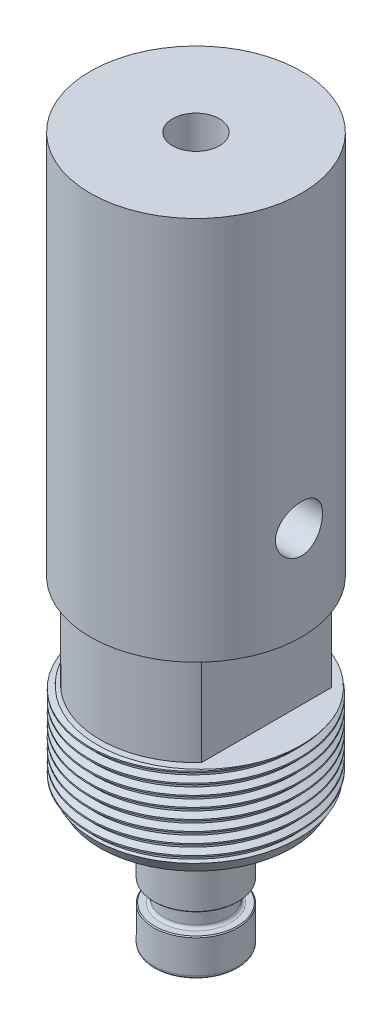
SolidWorks part; units mm, degrees
ref_plane "Front Plane" through (0, 0, 0) normal (0, 0, 1) x (1, 0, 0)
ref_plane "Top Plane" through (0, 0, 0) normal (0, 1, 0) x (1, 0, 0)
ref_plane "Right Plane" through (0, 0, 0) normal (1, 0, 0) x (0, 0, -1)
sketch "Sketch1" plane through (0, 0, 0) normal (0, 0, 1) x (1, 0, 0)
  line L0 (0, 50.6579) -> (0, -11.3733) construction
  line L1 (1.27, 0) -> (1.27, 87.1402)
  line L2 (1.27, 87.1402) -> (2.286, 88.9)
  line L3 (2.286, 88.9) -> (3.175, 88.9)
  line L4 (3.175, 88.9) -> (3.175, 95.25)
  line L5 (3.175, 95.25) -> (14.2875, 95.25)
  line L6 (14.2875, 95.25) -> (14.2875, 43.2816)
  line L7 (14.2875, 43.2816) -> (12.954, 43.2816)
  line L8 (12.954, 43.2816) -> (12.954, 30.5816)
  line L9 (12.954, 30.5816) -> (14.224, 30.5816)
  line L10 (14.224, 30.5816) -> (14.224, 20.0813)
  line L11 (14.224, 20.0813) -> (12.954, 17.8816)
  line L12 (12.954, 17.8816) -> (10.16, 17.8816)
  line L13 (10.16, 17.8816) -> (10.16, 19.3548)
  line L14 (10.16, 19.3548) -> (5.715, 19.3548)
  line L15 (5.715, 19.3548) -> (5.715, 7.8994)
  line L16 (5.715, 7.8994) -> (4.3434, 7.8994)
  line L17 (4.3434, 7.8994) -> (4.3434, 5.08)
  line L18 (5.715, 0) -> (1.27, 0)
  line L19 (4.3434, 5.08) -> (5.715, 5.08)
  line L20 (5.715, 5.08) -> (5.715, 0)
  point P20 (5.0292, 5.08)
  point P27 (13.589, 30.5816)
  dimension "D1" = 2.54
  dimension "D2" = 28.575
  dimension "D3" = 95.25
  dimension "D4" = 6.35
  dimension "D5" = 6.35
  dimension "D6" = 0.889
  dimension "D7" = 30
  dimension "D8" = 11.43
  dimension "D9" = 2.8194
  dimension "D10" = 8.6868
  dimension "D11" = 5.08
  dimension "D12" = 4.445
  dimension "D13" = 1.4732
  dimension "D14" = 11.4554
  dimension "D15" = 28.448
  dimension "D16" = 1.27
  dimension "D17" = 12.7
  dimension "D18" = 1.27
  dimension "D19" = 12.7
revolve "Revolve1" add sketch "Sketch1" angle 360 about L0
fillet "Fillet1" radius 0.508 1 edges at (0, 0, 5.715)
chamfer "Chamfer1" distance 0.127 angle 45 3 edges at (0, 17.8816, 10.16) (0, 5.08, 5.715) (0, 7.8994, 5.715)
fillet "Fillet2" radius 0.4064 4 edges at (0, 19.3548, 10.16) (0, 19.3548, 5.715) (0, 7.8994, 4.3434) (0, 5.08, 4.3434)
thread "Thread1" pitch 1.4111 method cut profile "Thread Profile1" start angle 0, offset 3.54, length 17.62, pitch 1.4111, diameter 28.448
ref_plane "Plane1" through (14.224, 16.5413, 0) normal (0, 0, 1) x (1, 0, 0)
sketch "Thread Profile1" plane through (14.224, 16.5413, 0) normal (0, 0, 1) x (1, 0, 0)
  line L0 (0, 0) -> (0, 1.4111) construction
  line L11 (0, 0) -> (0, 1.2347)
  line L12 (0, 1.2347) -> (-0.7638, 0.7937)
  line L13 (-0.7638, 0.7937) -> (-0.7638, 0.441)
  line L15 (-0.7638, 0.441) -> (0, 0)
  line L17 (-0.7638, 0.6174) -> (0, 0.6174) construction
  point P2 (0, 0)
  dimension "Pitch" = 1.4111
  dimension "Profile_Angle" = 60
  dimension "Profile_Land" = 0.3528
  dimension "Profile_Height" = 0.7638
sketch "Sketch6" plane through (0, 0, 0) normal (0, 0, 1) x (1, 0, 0)
  line L0 (19.2514, 43.2816) -> (9.525, 43.2816)
  line L1 (9.525, 43.2816) -> (9.525, 30.5816)
  line L2 (9.525, 30.5816) -> (19.2514, 30.5816)
  line L3 (19.2514, 30.5816) -> (19.2514, 43.2816)
  line L4 (-18.0058, 43.2816) -> (-9.525, 43.2816)
  line L5 (-12.954, 43.2816) -> (12.954, 43.2816) construction
  line L6 (-9.525, 43.2816) -> (-9.525, 30.5816)
  line L7 (-9.525, 30.5816) -> (-18.0058, 30.5816)
  line L8 (-18.0058, 30.5816) -> (-18.0058, 43.2816)
  line L9 (0, 0) -> (0, 96.7309) construction
  line L10 (-9.525, 36.9316) -> (9.525, 36.9316) construction
  point P16 (0, 36.9316)
  dimension "D1" = 12.7
  dimension "D2" = 19.05
extrude "Cut-Extrude1" cut sketch "Sketch6" against normal through all both and the other way through all contours L7 L8 L4 L6 | L3 L0 L1 L2
sketch "Sketch7" plane through (0, 0, 0) normal (0, 0, 1) x (1, 0, 0)
  line L0 (0, 85.09) -> (-19.7148, 85.09) construction
  line L1 (-17.0909, 88.265) -> (-7.9375, 88.265)
  line L2 (0, 85.09) -> (-17.0909, 85.09)
  line L4 (-7.9375, 88.265) -> (-7.9375, 86.36)
  line L5 (-7.9375, 86.36) -> (0, 86.36)
  line L6 (0, 86.36) -> (0, 85.09)
  line L7 (-17.0909, 88.265) -> (-17.0909, 85.09)
  line L8 (-14.2875, 95.25) -> (-14.2875, 43.2816) construction
  line L9 (14.2875, 95.25) -> (-14.2875, 95.25) construction
  dimension "D1" = 6.35
  dimension "D2" = 2.54
  dimension "D3" = 6.35
  dimension "D4" = 10.16
revolve "Cut-Revolve1" cut sketch "Sketch7" angle 360 about L0
sketch "Sketch8" plane through (0, 0, 0) normal (0, 0, 1) x (1, 0, 0)
  line L0 (-19.4823, 55.9816) -> (22.8333, 55.9816) construction
  line L1 (-18.2437, 55.9816) -> (-18.2437, 59.1566)
  line L2 (-18.2437, 59.1566) -> (-7.9375, 59.1566)
  line L3 (-7.9375, 59.1566) -> (-7.9375, 57.2516)
  line L4 (-7.9375, 57.2516) -> (7.9375, 57.2516)
  line L5 (7.9375, 57.2516) -> (7.9375, 59.1566)
  line L6 (7.9375, 59.1566) -> (18.5747, 59.1566)
  line L7 (18.5747, 59.1566) -> (18.5747, 55.9816)
  line L8 (-14.2875, 81.915) -> (-14.2875, 43.2816) construction
  line L9 (14.2875, 43.2816) -> (14.2875, 95.25) construction
  line L10 (-14.2875, 43.2816) -> (14.2875, 43.2816) construction
  line L11 (-18.2437, 55.9816) -> (18.5747, 55.9816)
  dimension "D1" = 6.35
  dimension "D2" = 6.35
  dimension "D3" = 6.35
  dimension "D4" = 2.54
  dimension "D5" = 12.7
revolve "Cut-Revolve2" cut sketch "Sketch8" angle 360 about L0
